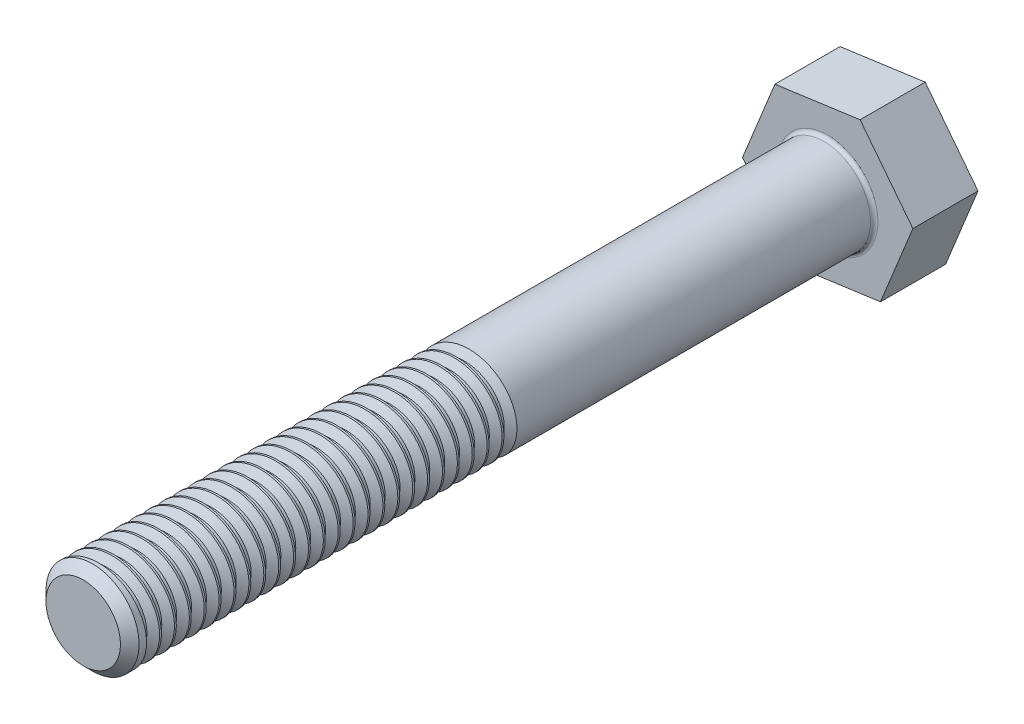
SolidWorks part; units mm, degrees
material "1060 Alloy"
ref_plane "Front Plane" through (0, 0, 0) normal (0, 0, 1) x (1, 0, 0)
ref_plane "Top Plane" through (0, 0, 0) normal (0, 1, 0) x (1, 0, 0)
ref_plane "Right Plane" through (0, 0, 0) normal (1, 0, 0) x (0, 0, -1)
sketch "Sketch1" plane through (0, 0, 0) normal (0, 0, 1) x (1, 0, 0)
  line L1 (2.8362, -3.6454) -> (4.5751, 0.6336)
  line L2 (4.5751, 0.6336) -> (1.7389, 4.279)
  line L3 (1.7389, 4.279) -> (-2.8362, 3.6454)
  line L4 (-2.8362, 3.6454) -> (-4.5751, -0.6336)
  line L5 (-4.5751, -0.6336) -> (-1.7389, -4.279)
  line L6 (-1.7389, -4.279) -> (2.8362, -3.6454)
  circle A0 centre (0, 0) radius 4 construction
  point P1 (3.7057, -1.5059)
  dimension "D1" = 8
extrude "Boss-Extrude1" add sketch "Sketch1" along normal blind 3.5
sketch "Sketch3" plane through (0, 0, 3.5) normal (0, 0, 1) x (1, 0, 0)
  circle A0 centre (0, 0) radius 2.5
  dimension "D1" = 5
extrude "Boss-Extrude2" add sketch "Sketch3" along normal blind 40
chamfer "Chamfer1" distance 0.5 angle 45 1 edges at (2.5, 0, 43.5)
fillet "Fillet1" radius 0.2 1 edges at (2.5, 0, 3.5)
thread "Thread1" pitch 0.8 method cut profile "Thread Profile1" start angle 0, offset 0, length 20, pitch 0.8, diameter 5
ref_plane "Plane1" through (-2.5, 0, 43) normal (0, -1, 0) x (-1, 0, 0)
sketch "Thread Profile1" plane through (-2.5, 0, 43) normal (0, -1, 0) x (-1, 0, 0)
  line L0 (0, 0) -> (0, 0.8) construction
  line L11 (0, 0) -> (0, 0.7)
  line L12 (0, 0.7) -> (-0.433, 0.45)
  line L13 (-0.433, 0.45) -> (-0.433, 0.25)
  line L15 (-0.433, 0.25) -> (0, 0)
  line L17 (-0.433, 0.35) -> (0, 0.35) construction
  point P2 (0, 0)
  dimension "Pitch" = 0.8
  dimension "Profile_Angle" = 60
  dimension "Profile_Land" = 0.2
  dimension "Profile_Height" = 0.433
